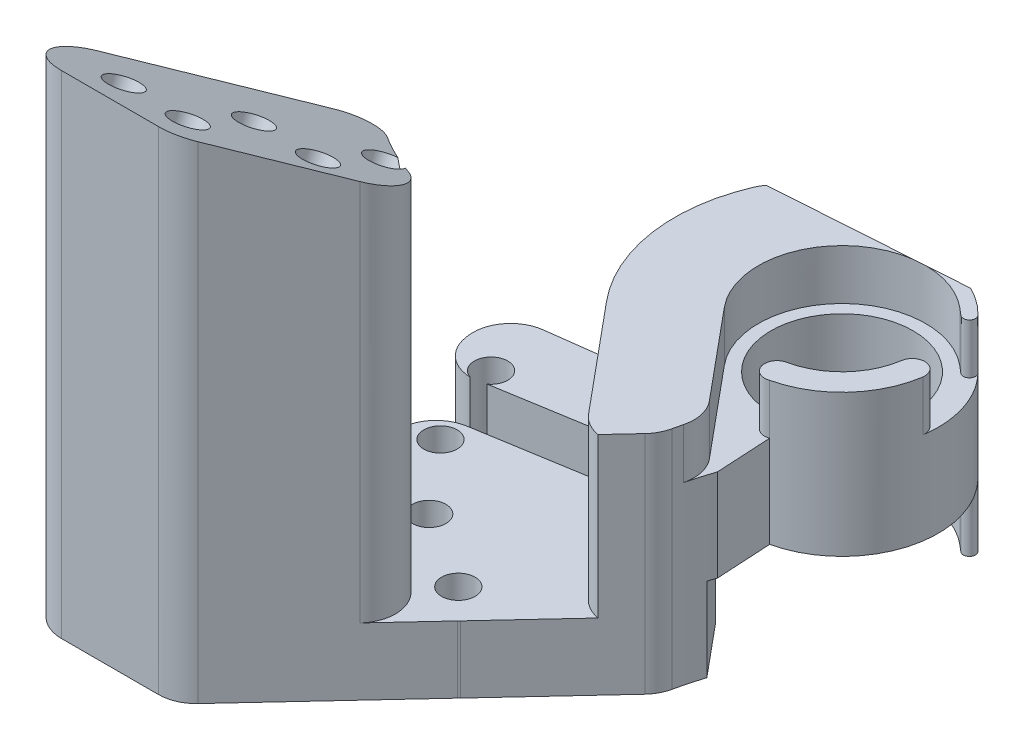
SolidWorks part; units mm, degrees
ref_plane "Front Plane" through (0, 0, 0) normal (0, 0, 1) x (1, 0, 0)
ref_plane "Top Plane" through (0, 0, 0) normal (0, 1, 0) x (1, 0, 0)
ref_plane "Right Plane" through (0, 0, 0) normal (1, 0, 0) x (0, 0, -1)
sketch "Sketch1" plane through (0, 0, 0) normal (0, 1, 0) x (1, 0, 0)
  line L0 (-100.7234, -106.6246) -> (-52.9347, -106.6246)
  line L1 (-52.9347, -106.6246) -> (-20.3562, -71.5817)
  line L2 (-100.7234, -106.6246) -> (-54.6408, -57.056)
  line L3 (-76.9804, 17.7489) -> (0, 23)
  line L4 (-60.0017, -36.0527) -> (0, 0) construction
  line L5 (0, 0) -> (-68.2059, -15.7466) construction
  line L6 (-68.2059, -15.7466) -> (-60.0017, -36.0527) construction
  line L7 (0, 23) -> (0, 17) construction
  line L8 (81.5493, -61.5) -> (18.6518, -14.0662) construction
  line L9 (5.1095, -22.4253) -> (5.844, -35.6405)
  line L10 (18.6518, -14.0662) -> (13.5729, -10.236) construction
  line L11 (-60.0017, -36.0527) -> (-45.9241, -52.8297) construction
  line L12 (-45.9241, -52.8297) -> (-27.3512, -64.4353) construction
  line L13 (-20.0273, -71.2442) -> (2.9659, -46.5117)
  line L14 (0, 0) -> (-59.9597, 0) construction
  circle A0 centre (0, 0) radius 17
  arc A1 (-20.3562, -71.5817) -> (-20.0273, -71.2442) centre (-27.3512, -64.4353) ccw
  arc A2 (5.1095, -22.4253) -> (0, 23) centre (0, 0) ccw
  arc A3 (-54.6408, -57.056) -> (-76.9804, 17.7489) centre (0, 0) cw
  circle A4 centre (0, 0) radius 70 construction
  circle A10 centre (-27.3512, -64.4353) radius 4
  circle A11 centre (-45.9241, -52.8297) radius 4
  circle A12 centre (-60.0017, -36.0527) radius 4
  circle A13 centre (-68.2059, -15.7466) radius 4
  arc A14 (5.844, -35.6405) -> (2.9659, -46.5117) centre (81.5493, -61.5) ccw
  dimension "D1" = 34
  dimension "D2" = 80
  dimension "D3" = 79
  dimension "D6" = 20
  dimension "D10" = 140
  dimension "D13" = 8
  dimension "D4" = 6
  dimension "D7" = 35
  dimension "D11" = 18
  dimension "D12" = 13
extrude "Boss-Extrude1" add sketch "Sketch1" along normal blind 180 contours A3 L2 L0 L1 A2 L3 A0 region at (-40.1615, 0, 35.8819)
sketch "Sketch8" plane through (0, 180, 0) normal (0, 1, 0) x (1, 0, 0)
  arc A0 (5.7542, -69.7631) -> (-61.2346, 33.9164) centre (0, 0) cw
  point P6 (-68.2059, -15.7466)
extrude "Cut-Extrude-Thin2" cut sketch "Sketch8" against normal blind 164 thin thin type mid plane wall 15
sketch "Sketch14" plane through (0, 16, 0) normal (0, 1, 0) x (1, 0, 0)
  line L0 (-50.505, -52.6073) -> (-59.2535, -62.0177)
  line L1 (-100.7234, -106.6246) -> (-54.6408, -57.056) construction
  arc A0 (-50.505, -52.6073) -> (-69.8213, 21.054) centre (0, 0) cw
  arc A1 (-69.8213, 21.054) -> (-86.4599, -36.8336) centre (-78.2054, -7.8712) ccw
  arc A2 (-86.4599, -36.8336) -> (-59.2535, -62.0177) centre (-14.3444, 13.7854) ccw
  arc A3 (-75.415, 17.8557) -> (-22.6987, -74.1014) centre (0, 0) ccw construction
extrude "Cut-Extrude5" cut sketch "Sketch14" along normal through all
sketch "Sketch4" plane through (0, 180, 0) normal (0, 1, 0) x (1, 0, 0)
  line L0 (-15.3792, -12.786) -> (41.4964, -81.1969)
  line L1 (41.4964, -81.1969) -> (80.7081, -42.4393)
  line L2 (80.7081, -42.4393) -> (12.9642, 15.2292)
  line L3 (5.1095, -22.4253) -> (5.844, -35.6405) construction
  arc A0 (12.9642, 15.2292) -> (-15.3792, -12.786) centre (0, 0) ccw
  arc A1 (-10.58, -35.768) -> (3.9649, -37.0887) centre (0, 0) ccw construction
  point P5 (5.9101, -36.8288)
  point P9 (61.1022, -61.8181)
  dimension "D1" = 20
  dimension "D2" = 37.3
  dimension "D3" = 1
extrude "Cut-Extrude2" cut sketch "Sketch4" against normal blind 138
sketch "Sketch5" plane through (0, 0, 0) normal (0, -1, 0) x (1, 0, 0)
  line L3 (12.9642, -15.2292) -> (80.7081, 42.4393)
  line L4 (12.9642, -15.2292) -> (80.7081, 42.4393)
  line L5 (80.7081, 42.4393) -> (41.4964, 81.1969)
  line L6 (80.7081, 42.4393) -> (41.4964, 81.1969)
  line L7 (41.4964, 81.1969) -> (-15.3792, 12.786)
  line L8 (41.4964, 81.1969) -> (-15.3792, 12.786)
  arc A1 (-15.3792, 12.786) -> (12.9642, -15.2292) centre (0, 0) ccw
  arc A2 (-15.3792, 12.786) -> (12.9642, -15.2292) centre (0, 0) ccw
  dimension "D1" = 0
extrude "Cut-Extrude3" cut sketch "Sketch5" against normal blind 20
sketch "Sketch6" plane through (0, 20, 0) normal (0, 1, 0) x (1, 0, 0)
  line L0 (2.2839, -13.8125) -> (-449.6067, -88.5326)
  line L2 (-459.7917, -45.4715) -> (-1.7993, 13.8839)
  circle A0 centre (0, 0) radius 14 construction
  dimension "D1" = 28
extrude "Cut-Extrude-Thin1" cut sketch "Sketch6" against normal blind 20 thin thin type mid plane wall 12
sketch "Sketch2" plane through (0, 0, 0) normal (1, 0, 0) x (0, 0, -1)
  line L0 (-119.5503, 123.4289) -> (73.0876, 37.5206)
  line L1 (73.0876, 37.5206) -> (54.8252, 250.3008)
  line L2 (54.8252, 250.3008) -> (-119.5503, 241.2433)
  line L3 (-119.5503, 241.2433) -> (-119.5503, 123.4289)
  line L5 (-9.9076, 74.5329) -> (-57.7616, 95.8737) construction
extrude "Cut-Extrude1" cut sketch "Sketch2" against normal through all and the other way through all
sketch "Sketch9" plane through (0, 42, 0) normal (0, 1, 0) x (1, 0, 0)
  line L0 (-1.5471, -16.9295) -> (5.3374, -26.525)
  line L1 (5.1095, -22.4253) -> (5.844, -35.6405) construction
  line L2 (16.904, 1.804) -> (22.9674, -1.2248)
  line L3 (5.1095, -22.4253) -> (5.3374, -26.525)
  circle A0 centre (0, 0) radius 17 construction
  arc A1 (5.1095, -22.4253) -> (21.6128, 7.8669) centre (0, 0) ccw construction
  arc A3 (-1.5471, -16.9295) -> (16.904, 1.804) centre (0, 0) ccw
  arc A5 (5.1095, -22.4253) -> (22.9674, -1.2248) centre (0, 0) ccw
extrude "Boss-Extrude2" add sketch "Sketch9" along normal blind 12
sketch "Sketch19" plane through (0, 54, 0) normal (0, 1, 0) x (1, 0, 0)
  circle A0 centre (0, 0) radius 77.5
  arc A1 (-53.6193, -55.9573) -> (-22.6987, -74.1014) centre (0, 0) ccw construction
extrude "Cut-Extrude10" cut sketch "Sketch19" along normal through all
sketch "Sketch20" plane through (0, 54, 0) normal (0, 1, 0) x (1, 0, 0)
  line L0 (5.2159, -37.5581) -> (-15.3792, -12.786) construction
  line L1 (12.9642, 15.2292) -> (21.6128, 7.8669) construction
  line L2 (5.2159, -37.5581) -> (-15.3792, -12.786) construction
  line L3 (12.9642, 15.2292) -> (21.6128, 7.8669) construction
  line L4 (-9.5522, -51.079) -> (-30.7584, -25.5719)
  line L5 (25.9285, 30.4584) -> (34.577, 23.0962)
  line L6 (-10.1633, -50.344) -> (-30.7584, -25.5719) construction
  line L7 (-7.4892, -72.2051) -> (-45.9241, -52.8297)
  line L8 (-45.9241, -52.8297) -> (-94.9403, 18.2741)
  line L9 (-94.9403, 18.2741) -> (-5.2158, 61.221)
  line L10 (-5.2158, 61.221) -> (34.577, 23.0962)
  line L11 (5.844, -35.6405) -> (6.0032, -38.5051) construction
  line L12 (-1.6007, -54.2661) -> (-7.4892, -72.2051)
  arc A0 (12.9642, 15.2292) -> (-15.3792, -12.786) centre (0, 0) ccw construction
  arc A1 (12.9642, 15.2292) -> (-15.3792, -12.786) centre (0, 0) ccw construction
  arc A2 (25.9285, 30.4584) -> (-30.7584, -25.5719) centre (0, 0) ccw
  arc A3 (-9.5522, -51.079) -> (-1.6007, -54.2661) centre (-2.6316, -45.3253) ccw
  dimension "D2" = 9
  dimension "D1" = 20
extrude "Cut-Extrude11" cut sketch "Sketch20" against normal up to surface (38 mm away) up to face at (-45.9241, 16, 56.8297)
fillet "Fillet1" radius 9 9 edges at (-52.9347, 58.8323, 106.6246) (-100.7234, 58.8323, 106.6246) (-53.6193, 55.5346, 55.9573) (-78.9703, 8, 2.1676) (-72.1399, 8, 32.1999) (-76.2359, 8, 20.7142) (-34.2492, 35, -20.6637) (2.9659, 27, 46.5117) (5.2159, 48, 37.5581)
sketch "Sketch13" plane through (0, 58.4835, -26.0811) normal (0, 0.9133, -0.4073) x (1, 0, 0)
  line L0 (-73.8544, -135.8114) -> (-58.5508, -135.8114) construction
  line L1 (-58.5508, -135.8114) -> (-56.5797, -120.6353) construction
  line L2 (-56.5797, -120.6353) -> (-41.2761, -120.6353) construction
  line L3 (-41.2761, -120.6353) -> (-39.3049, -105.4592) construction
  line L4 (-39.3049, -105.4592) -> (-24.0013, -105.4592) construction
  line L5 (-39.3049, -105.4592) -> (-73.8544, -135.8114) construction
  circle A0 centre (-73.8544, -135.8114) radius 4
  circle A1 centre (-56.5797, -120.6353) radius 4
  circle A2 centre (-39.3049, -105.4592) radius 4
  circle A3 centre (-24.0013, -105.4592) radius 4
  circle A4 centre (-41.2761, -120.6353) radius 4
  circle A5 centre (-58.5508, -135.8114) radius 4
  dimension "D1" = 8
extrude "Cut-Extrude4" cut sketch "Sketch13" against normal blind 10
sketch "Sketch15" plane through (0, 16, 0) normal (0, 1, 0) x (1, 0, 0)
  line L0 (-31.6409, -83.72) -> (0, -72.3157)
  line L1 (0, -72.3157) -> (-34.2545, -69.5189)
  line L2 (-22.6987, -74.1014) -> (-50.2647, -103.7526) construction
  arc A0 (-31.6409, -83.72) -> (-34.2545, -69.5189) centre (-38.2324, -77.5921) ccw
  arc A1 (-47.4138, -61.304) -> (-22.6987, -74.1014) centre (0, 0) ccw construction
  arc A2 (-47.4138, -61.304) -> (-39.6415, -66.5943) centre (0, 0) ccw construction
  arc A3 (-47.4138, -61.304) -> (-52.0031, -59.47) centre (-52.92, -68.4231) ccw construction
extrude "Cut-Extrude6" cut sketch "Sketch15" along normal through all
fillet "Fillet2" radius 9 3 edges at (-8.0493, 10, 21.6025) (-19.2065, 10, -5.5778) (-16.7797, 10, 10.8831)
sketch "Sketch16" plane through (0, 16, 0) normal (0, 1, 0) x (1, 0, 0)
  line L3 (-78.3631, 10.0115) -> (-36.9242, 15.3819)
  line L5 (-29.183, 21.0093) -> (-76.9804, 17.7489)
  line L6 (-78.3631, 10.0115) -> (-36.9242, 15.3819)
  line L8 (-29.183, 21.0093) -> (-76.9804, 17.7489)
  arc A2 (-76.9804, 17.7489) -> (-78.3631, 10.0115) centre (0, 0) ccw
  arc A3 (-36.8652, 15.5228) -> (-36.9242, 15.3819) centre (0, 0) ccw
  arc A4 (-76.9804, 17.7489) -> (-78.3631, 10.0115) centre (0, 0) ccw
  arc A5 (-36.8652, 15.5228) -> (-36.9242, 15.3819) centre (0, 0) ccw
  arc A7 (-29.183, 21.0093) -> (-36.8652, 15.5228) centre (-28.5705, 12.0302) ccw
  arc A8 (-29.183, 21.0093) -> (-36.8652, 15.5228) centre (-28.5705, 12.0302) ccw
  dimension "D1" = 0
extrude "Cut-Extrude7" cut sketch "Sketch16" against normal through all
sketch "Sketch18" plane through (0, 0, 0) normal (0, -1, 0) x (1, 0, 0)
  line L3 (-2.5705, -19.8341) -> (-36.9242, -15.3819)
  line L4 (-29.183, -21.0093) -> (0, -23)
  line L5 (21.6128, -7.8669) -> (12.9642, -15.2292)
  line L6 (-2.5705, -19.8341) -> (-36.9242, -15.3819)
  line L7 (-29.183, -21.0093) -> (0, -23)
  line L8 (21.6128, -7.8669) -> (12.9642, -15.2292)
  arc A3 (-36.9242, -15.3819) -> (-36.8652, -15.5228) centre (0, 0) ccw
  arc A4 (-36.9242, -15.3819) -> (-36.8652, -15.5228) centre (0, 0) ccw
  arc A6 (0, -23) -> (21.6128, -7.8669) centre (0, 0) ccw
  arc A7 (-2.5705, -19.8341) -> (12.9642, -15.2292) centre (0, 0) ccw
  arc A8 (-36.8652, -15.5228) -> (-29.183, -21.0093) centre (-28.5705, -12.0302) ccw
  arc A9 (-36.8652, -15.5228) -> (-29.183, -21.0093) centre (-28.5705, -12.0302) ccw
  arc A10 (0, -23) -> (21.6128, -7.8669) centre (0, 0) ccw
  arc A11 (-2.5705, -19.8341) -> (12.9642, -15.2292) centre (0, 0) ccw
  dimension "D1" = 0
extrude "Cut-Extrude9" cut sketch "Sketch18" against normal blind 5
chamfer "Chamfer1" distance 2 angle 45 1 edges at (-14.5915, 5, -22.0047) tangent propagation no
fillet "Fillet5" radius 3 4 edges at (-1.5471, 48, 16.9295) (16.904, 48, -1.804) (22.9674, 48, 1.2248) (5.3374, 48, 26.525)
fillet "Fillet6" radius 1.45 2 edges at (21.6128, 12.5, -7.8669) (21.6128, 48, -7.8669)
chamfer "Chamfer2" distance 3 angle 45 1 edges at (-14.5915, 54, -22.0047) tangent propagation no
